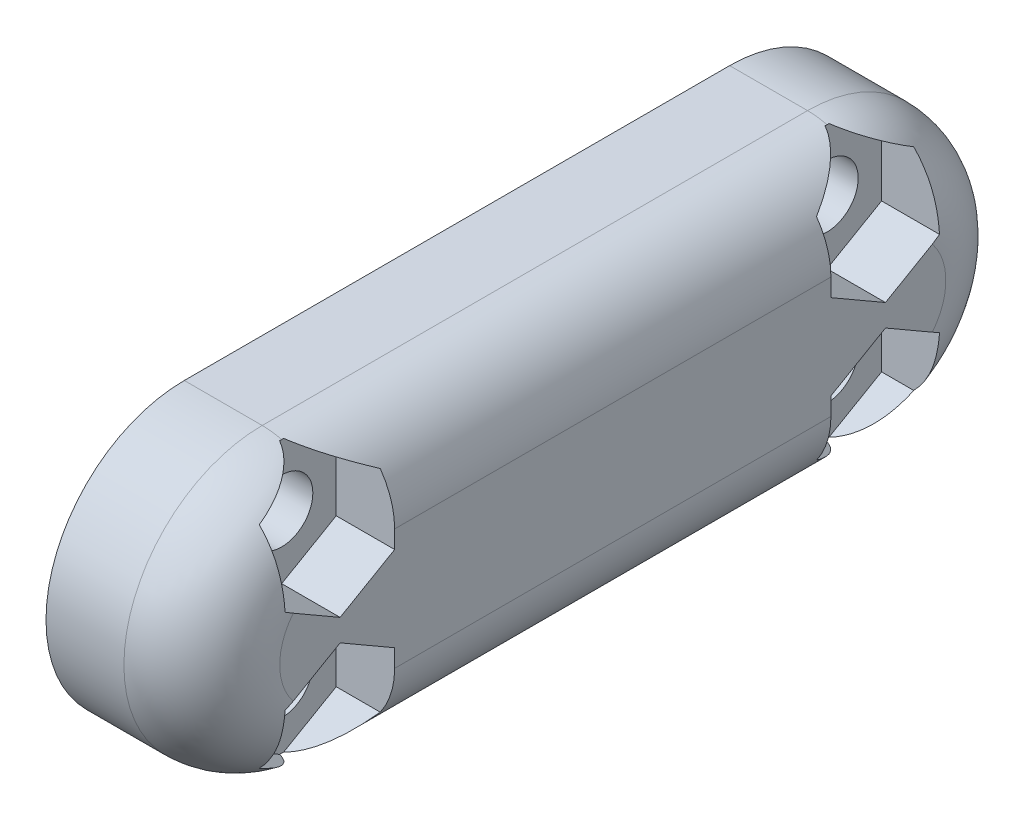
SolidWorks part; units mm, degrees
ref_plane "Front Plane" through (0, 0, 0) normal (0, 0, 1) x (1, 0, 0)
ref_plane "Top Plane" through (0, 0, 0) normal (0, 1, 0) x (1, 0, 0)
ref_plane "Right Plane" through (0, 0, 0) normal (1, 0, 0) x (0, 0, -1)
sketch "Sketch1" plane through (0, 0, 0) normal (1, 0, 0) x (0, 0, -1)
  line L0 (0, 2) -> (0, -2) construction
  line L1 (0, 5.6) -> (21, 5.6) construction
  line L2 (0, 5.6) -> (0, 2) construction
  line L3 (0, 2) -> (21, 2) construction
  line L4 (21, 5.6) -> (21, 2) construction
  line L5 (0, -2) -> (21, -2) construction
  line L6 (0, -2) -> (0, -5.6) construction
  line L7 (0, -5.6) -> (21, -5.6) construction
  line L8 (21, -2) -> (21, -5.6) construction
  line L9 (21, 2) -> (21, -2) construction
  point P8 (0, 0)
  dimension "D1" = 3.6
  dimension "D2" = 4
  dimension "D3" = 3.6
  dimension "D4" = 21
sketch "Sketch2" plane through (0, 0, 0) normal (1, 0, 0) x (0, 0, -1)
  line L0 (0, 5.6) -> (21, 5.6) construction
  line L1 (-3.5, 7.1) -> (24.5, 7.1)
  line L2 (-3.5, 7.1) -> (-3.5, -7.1) construction
  line L3 (-3.5, -7.1) -> (24.5, -7.1)
  line L4 (24.5, 7.1) -> (24.5, -7.1) construction
  line L5 (0, -5.6) -> (21, -5.6) construction
  line L6 (0, 5.6) -> (0, 2) construction
  line L8 (21, 5.6) -> (21, 2) construction
  line L9 (-3.5, 3.8) -> (24.5, 3.8) construction
  line L10 (24.5, -3.8) -> (-3.5, -3.8) construction
  line L11 (0, -2) -> (0, -5.6) construction
  arc A0 (-3.5, 7.1) -> (-3.5, -7.1) centre (-3.5, 0) ccw
  arc A1 (24.5, 7.1) -> (24.5, -7.1) centre (24.5, 0) cw
  point P20 (0, -3.8)
  point P21 (0, 3.8)
  dimension "D1" = 1.5
  dimension "D2" = 1.5
  dimension "D3" = 3.5
  dimension "D4" = 3.5
extrude "Boss-Extrude1" add sketch "Sketch2" along normal blind 8
sketch "Sketch4" plane through (0, 0, 0) normal (0, 0, 1) x (1, 0, 0)
  line L0 (0, 5.6) -> (0, 2) construction
  line L1 (0, 2) -> (2, 2)
  line L2 (0, 2) -> (0, -2)
  line L3 (0, -2) -> (2, -2)
  line L4 (2, 2) -> (2, -2)
  point P6 (0, 0)
  dimension "D1" = 2
  dimension "D2" = 4
extrude "Cut-Extrude5" cut sketch "Sketch4" against normal up to next
sketch "Sketch5" plane through (0, 0, 0) normal (1, 0, 0) x (0, 0, -1)
  line L1 (21, 5.6) -> (0, 5.6)
  line L2 (21, 5.6) -> (21, 2)
  line L3 (21, 2) -> (0, 2)
  line L4 (0, 5.6) -> (0, 2)
  line L5 (21, -2) -> (0, -2)
  line L6 (21, -2) -> (21, -5.6)
  line L7 (21, -5.6) -> (0, -5.6)
  line L8 (0, -2) -> (0, -5.6)
extrude "Cut-Extrude2" cut sketch "Sketch5" along normal blind 6.75
sketch "Sketch6" plane through (8, 0, 0) normal (1, 0, 0) x (0, 0, -1)
  circle A0 centre (-3.5, 3.8) radius 1.6
  circle A1 centre (-3.5, -3.8) radius 1.6
  circle A2 centre (24.5, 3.8) radius 1.6
  circle A3 centre (24.5, -3.8) radius 1.6
  dimension "D1" = 3.2
extrude "Cut-Extrude3" cut sketch "Sketch6" along direction (1, 0, 0) on the side against the normal up to next (8 mm away)
sketch "Sketch7" plane through (8, 0, 0) normal (1, 0, 0) x (0, 0, -1)
  line L1 (-0.7, 2.1834) -> (-0.7, 5.4166)
  line L2 (-0.7, 5.4166) -> (-3.5, 7.0332)
  line L3 (-3.5, 7.0332) -> (-6.3, 5.4166)
  line L4 (-6.3, 5.4166) -> (-6.3, 2.1834)
  line L5 (-6.3, 2.1834) -> (-3.5, 0.5668)
  line L6 (-3.5, 0.5668) -> (-0.7, 2.1834)
  line L7 (21.7, 5.4166) -> (21.7, 2.1834)
  line L8 (21.7, 2.1834) -> (24.5, 0.5668)
  line L9 (24.5, 0.5668) -> (27.3, 2.1834)
  line L10 (27.3, 2.1834) -> (27.3, 5.4166)
  line L11 (27.3, 5.4166) -> (24.5, 7.0332)
  line L12 (24.5, 7.0332) -> (21.7, 5.4166)
  line L13 (21.7, -2.1834) -> (21.7, -5.4166)
  line L14 (21.7, -5.4166) -> (24.5, -7.0332)
  line L15 (24.5, -7.0332) -> (27.3, -5.4166)
  line L16 (27.3, -5.4166) -> (27.3, -2.1834)
  line L17 (27.3, -2.1834) -> (24.5, -0.5668)
  line L18 (24.5, -0.5668) -> (21.7, -2.1834)
  line L19 (-3.5, -7.0332) -> (-0.7, -5.4166)
  line L20 (-0.7, -5.4166) -> (-0.7, -2.1834)
  line L21 (-0.7, -2.1834) -> (-3.5, -0.5668)
  line L22 (-3.5, -0.5668) -> (-6.3, -2.1834)
  line L23 (-6.3, -2.1834) -> (-6.3, -5.4166)
  line L24 (-6.3, -5.4166) -> (-3.5, -7.0332)
  line L26 (-3.5, 7.1) -> (-3.5, -7.1) construction
  line L27 (24.5, 7.1) -> (24.5, -7.1) construction
  circle A0 centre (-3.5, 3.8) radius 2.8 construction
  circle A1 centre (24.5, 3.8) radius 2.8 construction
  circle A2 centre (24.5, -3.8) radius 2.8 construction
  circle A3 centre (-3.5, -3.8) radius 2.8 construction
  dimension "D1" = 5.6
extrude "Cut-Extrude4" cut sketch "Sketch7" against normal blind 3
fillet "Fillet1" radius 4 4 edges at (8, 7.1, -10.5) (8, 0, -31.6) (8, -7.1, -10.5) (8, 0, 10.6)
